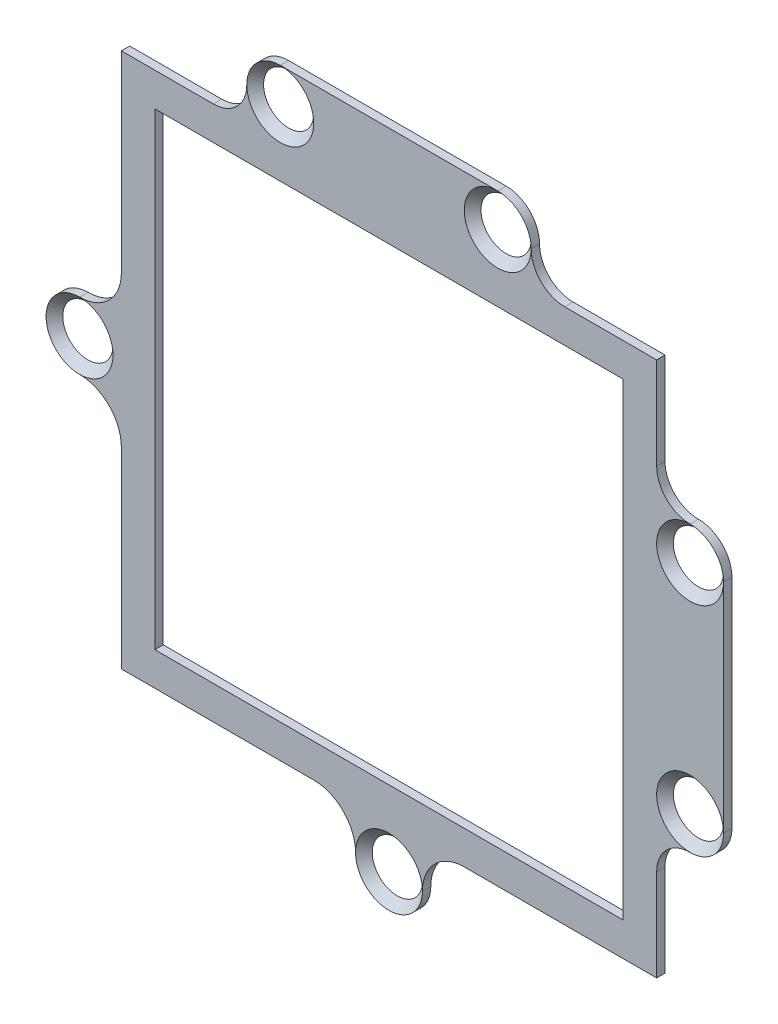
SolidWorks part; units mm, degrees
ref_plane "Top Plane" through (0, 0, 0) normal (0, 0, 1) x (1, 0, 0)
ref_plane "Right Plane" through (0, 0, 0) normal (0, 1, 0) x (1, 0, 0)
ref_plane "Front Plane" through (0, 0, 0) normal (1, 0, 0) x (0, 0, -1)
sketch "Sketch1" plane through (0, 0, 0) normal (0, 0, 1) x (1, 0, 0)
  line L44 (40, -13) -> (40, -9) construction
  line L47 (28, -28) -> (-28, -28) construction
  line L48 (-28, -28) -> (-28, 28) construction
  line L49 (-28, 28) -> (-9, 28) construction
  line L52 (-21, 32) -> (-32, 32) construction
  line L53 (-32, 32) -> (-32, 9) construction
  line L54 (-32, -9) -> (-32, -32) construction
  line L55 (-32, -32) -> (-9, -32) construction
  line L56 (9, -32) -> (32, -32) construction
  line L57 (32, -32) -> (32, -21) construction
  line L60 (32, 21) -> (32, 32) construction
  line L61 (32, 32) -> (21, 32) construction
  line L62 (13, 40) -> (9, 40) construction
  line L65 (28, 28) -> (28, 9) construction
  line L66 (40, -13) -> (40, 13)
  line L69 (28, -28) -> (-28, -28)
  line L70 (-28, -28) -> (-28, 28)
  line L71 (-28, 28) -> (28, 28)
  line L74 (-21, 32) -> (-32, 32)
  line L75 (-32, 32) -> (-32, 9)
  line L76 (-32, -9) -> (-32, -32)
  line L77 (-32, -32) -> (-9, -32)
  line L78 (9, -32) -> (32, -32)
  line L79 (32, -32) -> (32, -21)
  line L82 (32, 21) -> (32, 32)
  line L83 (32, 32) -> (21, 32)
  line L84 (13, 40) -> (-13, 40)
  line L87 (28, 28) -> (28, -28)
  arc A40 (36, -17) -> (40, -13) centre (36, -13) ccw construction
  arc A41 (-13, 40) -> (-17, 36) centre (-13, 36) ccw construction
  arc A42 (-21, 32) -> (-17, 36) centre (-21, 36) ccw construction
  arc A43 (-37, 4) -> (-32, 9) centre (-37, 9) ccw construction
  arc A44 (-37, 4) -> (-37, -4) centre (-37, 0) ccw construction
  arc A45 (-32, -9) -> (-37, -4) centre (-37, -9) ccw construction
  arc A46 (-4, -37) -> (-9, -32) centre (-9, -37) ccw construction
  arc A47 (-4, -37) -> (4, -37) centre (0, -37) ccw construction
  arc A48 (9, -32) -> (4, -37) centre (9, -37) ccw construction
  arc A49 (36, -17) -> (32, -21) centre (36, -21) ccw construction
  arc A50 (40, 13) -> (36, 17) centre (36, 13) ccw construction
  arc A51 (32, 21) -> (36, 17) centre (36, 21) ccw construction
  arc A52 (17, 36) -> (21, 32) centre (21, 36) ccw construction
  arc A53 (17, 36) -> (13, 40) centre (13, 36) ccw construction
  arc A54 (36, -17) -> (40, -13) centre (36, -13) ccw
  arc A55 (-13, 40) -> (-17, 36) centre (-13, 36) ccw
  arc A56 (-21, 32) -> (-17, 36) centre (-21, 36) ccw
  arc A57 (-37, 4) -> (-32, 9) centre (-37, 9) ccw
  arc A58 (-37, 4) -> (-37, -4) centre (-37, 0) ccw
  arc A59 (-32, -9) -> (-37, -4) centre (-37, -9) ccw
  arc A60 (-4, -37) -> (-9, -32) centre (-9, -37) ccw
  arc A61 (-4, -37) -> (4, -37) centre (0, -37) ccw
  arc A62 (9, -32) -> (4, -37) centre (9, -37) ccw
  arc A63 (36, -17) -> (32, -21) centre (36, -21) ccw
  arc A64 (40, 13) -> (36, 17) centre (36, 13) ccw
  arc A65 (32, 21) -> (36, 17) centre (36, 21) ccw
  arc A66 (17, 36) -> (21, 32) centre (21, 36) ccw
  arc A67 (17, 36) -> (13, 40) centre (13, 36) ccw
  circle A68 centre (-37, 0) radius 2 construction
  circle A69 centre (-13, 36) radius 2 construction
  circle A70 centre (0, -37) radius 2 construction
  circle A71 centre (36, -13) radius 2 construction
  circle A72 centre (36, 13) radius 2 construction
  circle A73 centre (13, 36) radius 2 construction
  circle A74 centre (-37, 0) radius 2
  circle A75 centre (-13, 36) radius 2
  circle A76 centre (0, -37) radius 2
  circle A77 centre (36, -13) radius 2
  circle A78 centre (36, 13) radius 2
  circle A79 centre (13, 36) radius 2
extrude "Boss-Extrude1" add sketch "Sketch1" along normal blind 1
chamfer "Chamfer1" distance 2 angle 45 6 edges at (15, 36, 1) (-11, 36, 1) (-35, 0, 1) (38, -13, 1) (2, -37, 1) (38, 13, 1)
ref_plane "Plane1" through (0, 0, 0.5) normal (0, 0, 1) x (1, 0, 0)
sketch "Sketch2" plane through (0, 0, 0.5) normal (0, 0, 1) x (1, 0, 0)
  line L0 (20, 28) -> (28, 20)
  line L1 (28, 20) -> (28, 28)
  line L2 (28, 28) -> (20, 28)
  line L3 (24, 28) -> (26, 26) construction
  line L4 (26, 26) -> (28, 24) construction
  line L6 (24, 24) -> (26, 26) construction
  circle A0 centre (26, 26) radius 1.25
  dimension "D1" = 8
  dimension "D2" = 2.5
extrude "Boss-Extrude2" [suppressed] add sketch "Sketch2" along normal mid plane 1
ref_axis "Axis1" [suppressed] through (0, 0, 5.25) along (0, 0, -1)
pattern_circular "CirPattern1" [suppressed] count 4 every 90 about axis through (0, 0, 5.25) along (0, 0, -1) of bodies 105
